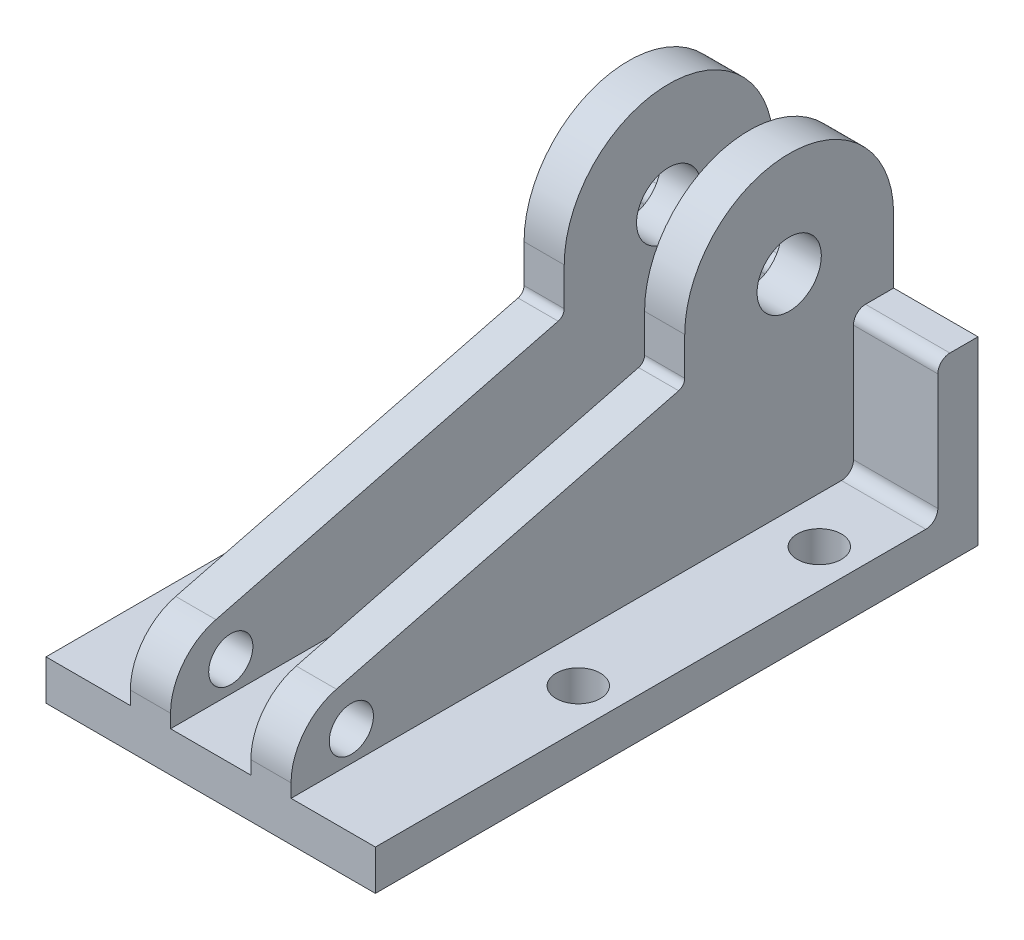
SolidWorks part; units mm, degrees
ref_plane "Front Plane" through (0, 0, 0) normal (0, 0, 1) x (1, 0, 0)
ref_plane "Top Plane" through (0, 0, 0) normal (0, 1, 0) x (1, 0, 0)
ref_plane "Right Plane" through (0, 0, 0) normal (1, 0, 0) x (0, 0, -1)
sketch "Sketch1" plane through (0, 0, 0) normal (0, 1, 0) x (1, 0, 0)
  line L1 (-41, -75) -> (41, -75)
  line L2 (-41, -75) -> (-41, 75)
  line L3 (-41, 75) -> (41, 75)
  line L4 (41, -75) -> (41, 75)
  line L5 (-41, -75) -> (41, 75) construction
  line L6 (-41, 75) -> (41, -75) construction
  point P0 (0, 0)
  dimension "D1" = 82
  dimension "D2" = 150
extrude "Boss-Extrude1" add sketch "Sketch1" along normal blind 10
sketch "Sketch2" plane through (41, 0, 0) normal (1, 0, 0) x (0, 0, -1)
  line L1 (75, 0) -> (65, 0)
  line L2 (75, 0) -> (75, 45)
  line L3 (75, 45) -> (65, 45)
  line L4 (65, 0) -> (65, 45)
  dimension "D1" = 10
  dimension "D2" = 45
extrude "Boss-Extrude2" add sketch "Sketch2" against normal through all
sketch "Sketch3" plane through (0, 0, -65) normal (0, 0, 1) x (1, 0, 0)
  line L0 (-41, 45) -> (41, 45) construction
  line L2 (10, 45) -> (10, 10)
  line L3 (10, 10) -> (20, 10)
  line L4 (20, 45) -> (20, 10)
  line L5 (-41, 10) -> (41, 10) construction
  line L6 (41, 45) -> (41, 10) construction
  line L7 (0, -55) -> (0, 55) construction
  line L9 (10, 45) -> (10, 87)
  line L10 (10, 87) -> (20, 87)
  line L11 (20, 45) -> (20, 87)
  line L12 (-10, 45) -> (-10, 87)
  line L13 (-10, 87) -> (-20, 87)
  line L14 (-20, 45) -> (-20, 87)
  line L15 (-20, 45) -> (-20, 10)
  line L16 (-10, 10) -> (-20, 10)
  line L17 (-10, 45) -> (-10, 10)
  dimension "D1" = 21
  dimension "D2" = 10
  dimension "D3" = 42
extrude "Boss-Extrude3" add sketch "Sketch3" along normal blind 42 and the other way blind 10
fillet "Fillet3" 2 edges at (15, 87, -23) (15, 87, -75) type full round first side face at (15, 48.5, -23) second side face at (0, 51.5, -75) middle face at (15, 87, -49)
fillet "Fillet4" 2 edges at (-15, 87, -23) (-15, 87, -75) type full round first side face at (-15, 48.5, -23) second side face at (0, 47.1667, -75) middle face at (-15, 87, -49)
sketch "Sketch4" plane through (20, 0, 0) normal (1, 0, 0) x (0, 0, -1)
  line L0 (23, 10) -> (23, 50)
  line L1 (23, 10) -> (23, 61) construction
  line L2 (23, 50) -> (-75, 25)
  line L3 (-75, 25) -> (-75, 10)
  line L4 (-75, 10) -> (23, 10)
  dimension "D1" = 15
  dimension "D2" = 40
extrude "Boss-Extrude4" add sketch "Sketch4" against normal up to surface (10 mm away) up to face at (10, 43, -54.3333)
sketch "Sketch5" plane through (-20, 0, 0) normal (-1, 0, 0) x (0, 0, 1)
  line L0 (-23, 50) -> (75, 25)
  line L1 (75, 25) -> (75, 10)
  line L2 (75, 10) -> (-23, 10)
  line L3 (-23, 10) -> (-23, 50)
extrude "Boss-Extrude5" add sketch "Sketch5" against normal up to surface (10 mm away) up to face at (-10, 43, -54.3333)
fillet "Fillet5" radius 15 1 edges at (15, 25, 75)
fillet "Fillet6" radius 15 1 edges at (-15, 25, 75)
sketch "Sketch6" plane through (20, 0, 0) normal (1, 0, 0) x (0, 0, -1)
  line L0 (65, 10) -> (-75, 10) construction
  line L1 (-75, 10) -> (-75, 0) construction
  circle A0 centre (49, 61) radius 8
  circle A1 centre (-60, 17.5) radius 5.5
  dimension "D1" = 7.5
  dimension "D3" = 11
  dimension "D2" = 15
extrude "Cut-Extrude1" cut sketch "Sketch6" against normal through all
fillet "Fillet7" radius 3 1 edges at (30.5, 45, -65)
fillet "Fillet8" radius 3 1 edges at (0, 45, -65)
fillet "Fillet9" radius 3 1 edges at (-30.5, 45, -65)
fillet "Fillet10" radius 3 3 edges at (-30.5, 10, -65) (0, 10, -65) (30.5, 10, -65)
fillet "Fillet11" radius 2 2 edges at (-15, 50, -23) (15, 50, -23)
sketch "Sketch7" plane through (0, 10, 0) normal (0, 1, 0) x (1, 0, 0)
  line L0 (20, 75) -> (41, 75) construction
  line L1 (20, 62) -> (20, -75) construction
  line L3 (20, 21.4944) -> (20, -63.7078) construction
  line L4 (0, -55) -> (0, 55) construction
  circle A0 centre (31.5, 45) radius 5.5
  circle A1 centre (31.5, -15) radius 5.5
  circle A2 centre (-31.5, -15) radius 5.5
  circle A3 centre (-31.5, 45) radius 5.5
  point P8 (0, 0)
  point P11 (0, 0)
  dimension "D1" = 30
  dimension "D3" = 11
  dimension "D4" = 11.5
  dimension "D6" = 11
  dimension "D2" = 11.5
  dimension "D5" = 60
extrude "Cut-Extrude2" cut sketch "Sketch7" against normal through all
